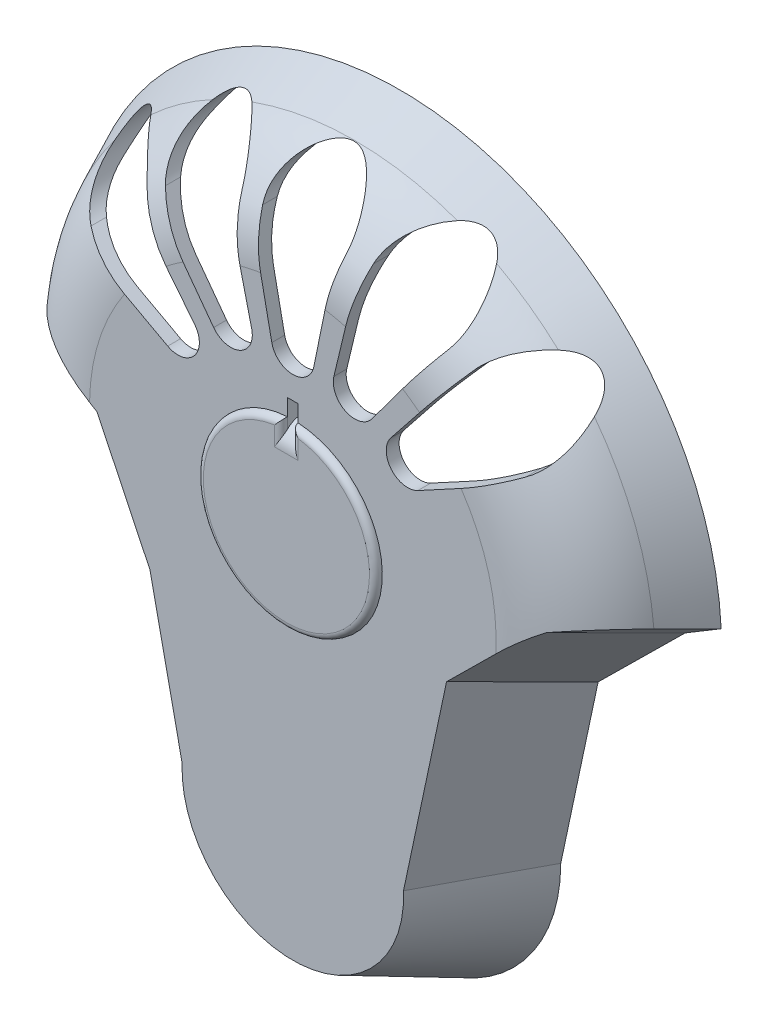
SolidWorks part; units mm, degrees
ref_plane "Front Plane" through (0, 0, 0) normal (0, 0, 1) x (1, 0, 0)
ref_plane "Top Plane" through (0, 0, 0) normal (0, 1, 0) x (1, 0, 0)
ref_plane "Right Plane" through (0, 0, 0) normal (1, 0, 0) x (0, 0, -1)
sketch "Sketch2" plane through (0, 0, 0) normal (0, 0, 1) x (1, 0, 0)
  line L0 (0, 0) -> (0, 30.6965) construction
  line L1 (-19.05, 0) -> (-24.4489, 25.4)
  line L2 (-24.4489, 25.4) -> (-38.0562, 33.5761)
  line L3 (24.4489, 25.4) -> (38.0562, 33.5761)
  line L4 (19.05, 0) -> (24.4489, 25.4)
  arc A0 (-38.0562, 33.5761) -> (38.0562, 33.5761) centre (0, 31.75) cw
  arc A1 (-19.05, 0) -> (19.05, 0) centre (0, 0) ccw
  point P11 (14.3442, -23.6201)
  point P12 (0, 2.1853)
  dimension "D1" = 38.1
  dimension "D5" = 19.05
  dimension "D2" = 24
  dimension "D3" = 118
  dimension "D4" = 31.75
  dimension "D6" = 25.4
  dimension "D7" = 25.4
extrude "Boss-Extrude1" add sketch "Sketch2" along normal blind 12.7 draft 25
fillet "Fillet1" radius 12.7 1 edges at (0, 63.9279, 12.7)
chamfer "Chamfer1" distance 4.5974 angle 30 1 edges at (21.8203, 27.275, 6.35) first distance on face at (18.2098, 13.8494, 7.9375)
chamfer "Chamfer2" distance 4.5974 angle 30 1 edges at (-21.8203, 27.275, 6.35) first distance on face at (-28.3158, 31.4944, 6.9317)
shell "Shell1" thickness 1.524 removed face at (0.8301, 22.3449, 0)
sketch "Sketch3" plane through (0, 0, 0) normal (0, 0, 1) x (1, 0, 0)
  line L0 (0, 0) -> (0, 72.7901) construction
  line L1 (-4.9774, 61.214) -> (-2.4887, 49.022)
  line L2 (4.9774, 61.214) -> (2.4887, 49.022)
  line L3 (7.7647, 61.3284) -> (4.8677, 49.2269)
  line L4 (16.7868, 57.1213) -> (9.3787, 47.1234)
  line L5 (19.3613, 56.047) -> (11.6214, 46.3037)
  line L6 (25.7601, 48.4212) -> (14.8208, 42.4908)
  line L7 (1.6516, 32.5332) -> (2.4887, 49.022) construction
  line L8 (1.6516, 32.5332) -> (9.3787, 47.1234) construction
  line L9 (-25.7601, 48.4212) -> (-14.8208, 42.4908)
  line L10 (-19.3613, 56.047) -> (-11.6214, 46.3037)
  line L11 (-7.7647, 61.3284) -> (-4.8677, 49.2269)
  line L12 (-16.7868, 57.1213) -> (-9.3787, 47.1234)
  line L13 (-4.9774, 61.214) -> (-2.4887, 49.022)
  line L14 (4.9774, 61.214) -> (2.4887, 49.022)
  arc A0 (-4.9774, 61.214) -> (4.9774, 61.214) centre (0, 62.23) cw
  arc A1 (2.4887, 49.022) -> (-2.4887, 49.022) centre (0, 49.53) cw
  arc A2 (38.0562, 33.5761) -> (-38.0562, 33.5761) centre (0, 31.75) ccw construction
  arc A3 (9.3787, 47.1234) -> (4.8677, 49.2269) centre (7.3379, 48.6355) cw
  arc A4 (7.7647, 61.3284) -> (16.7868, 57.1213) centre (12.7051, 60.1456) cw
  arc A5 (14.8208, 42.4908) -> (11.6214, 46.3037) centre (13.6103, 44.7237) cw
  arc A6 (19.3613, 56.047) -> (25.7601, 48.4212) centre (23.339, 52.8871) cw
  arc A7 (-19.3613, 56.047) -> (-25.7601, 48.4212) centre (-23.339, 52.8871) ccw
  arc A8 (-14.8208, 42.4908) -> (-11.6214, 46.3037) centre (-13.6103, 44.7237) ccw
  arc A9 (-9.3787, 47.1234) -> (-4.8677, 49.2269) centre (-7.3379, 48.6355) ccw
  arc A10 (-7.7647, 61.3284) -> (-16.7868, 57.1213) centre (-12.7051, 60.1456) ccw
  dimension "D1" = 5.08
  dimension "D2" = 2.54
  dimension "D3" = 12.7
  dimension "D4" = 17.78
  dimension "D6" = 25
  dimension "D7" = 16.51
  dimension "D5" = 3
extrude "Cut-Extrude15" cut sketch "Sketch3" along normal through all contours L9 A8 L10 A7 | L11 A10 L12 A9 | A1 L2 A0 L1 | A4 L3 A3 L4 | A6 L5 A5 L6 region at (0, 58.147, 0) region at (10.9796, 56.4452, 0) region at (20.2113, 50.2627, 0) region at (-20.2113, 50.2627, 0) region at (-10.9796, 56.4452, 0)
sketch "Sketch4" plane through (0, 0, 12.7) normal (0, 0, 1) x (1, 0, 0)
  circle A0 centre (0, 31.75) radius 10.6045
  dimension "D1" = 21.209
extrude "Boss-Extrude2" add sketch "Sketch4" along normal blind 0.762
sketch "Sketch5" plane through (0, 0, 13.462) normal (0, 0, 1) x (1, 0, 0)
  line L0 (0, 31.75) -> (0, -8.1015) construction
  line L2 (-0.635, 44.3049) -> (0.635, 44.3049)
  line L3 (-0.635, 44.3049) -> (-0.635, 41.7649)
  line L4 (-0.635, 41.7649) -> (0.635, 41.7649)
  line L5 (0.635, 44.3049) -> (0.635, 41.7649)
  line L6 (-0.635, 44.3049) -> (0.635, 41.7649) construction
  line L7 (-0.635, 41.7649) -> (0.635, 44.3049) construction
  point P1 (0, 43.0349)
  dimension "D1" = 2.54
  dimension "D2" = 1.27
extrude "Cut-Extrude16" cut sketch "Sketch5" against normal through all
fillet "Fillet4" radius 2.54 1 edges at (0, 41.7649, 13.462)
fillet "Fillet7" radius 0.762 3 edges at (0, 21.1455, 13.462) (-0.635, 40.7865, 13.462) (0.635, 40.7865, 13.462)
